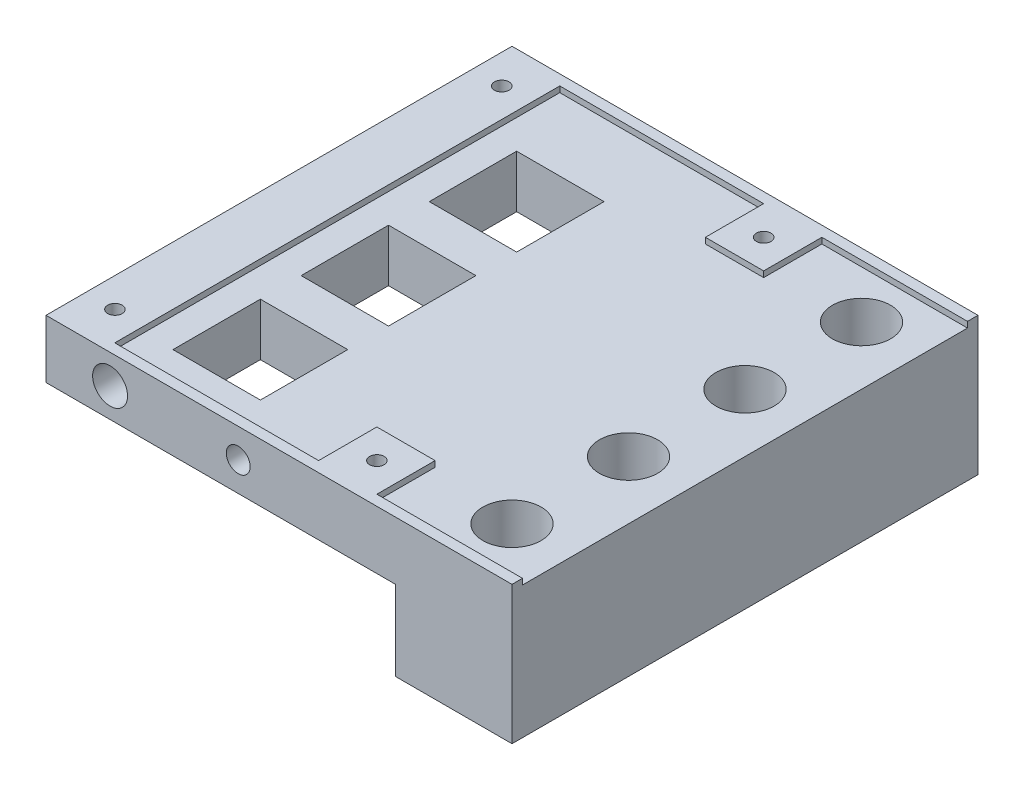
SolidWorks part; units mm, degrees
ref_plane "Front Plane" through (0, 0, 0) normal (0, 0, 1) x (1, 0, 0)
ref_plane "Top Plane" through (0, 0, 0) normal (0, 1, 0) x (1, 0, 0)
ref_plane "Right Plane" through (0, 0, 0) normal (1, 0, 0) x (0, 0, -1)
sketch "Sketch1" plane through (0, 0, 0) normal (0, 1, 0) x (1, 0, 0)
  line L1 (-77.5607, 49.5304) -> (2.4393, 49.5304)
  line L2 (-77.5607, 49.5304) -> (-77.5607, -30.4696)
  line L3 (-77.5607, -30.4696) -> (2.4393, -30.4696)
  line L4 (2.4393, 49.5304) -> (2.4393, -30.4696)
  dimension "D1" = 80
  dimension "D2" = 80
extrude "Boss-Extrude1" add sketch "Sketch1" along normal blind 23.7
sketch "Sketch2" plane through (0, 23.7, 0) normal (0, 1, 0) x (1, 0, 0)
  line L0 (2.4393, -30.4696) -> (2.4393, 49.5304) construction
  line L1 (2.4393, -28.6696) -> (-22.5607, -28.6696)
  line L2 (2.4393, -28.6696) -> (2.4393, 47.7304)
  line L3 (2.4393, 47.7304) -> (-22.5607, 47.7304)
  line L4 (-67.5607, -28.6696) -> (-67.5607, 47.7304)
  line L5 (-77.5607, 49.5304) -> (-77.5607, -30.4696) construction
  line L6 (-77.5607, 9.5304) -> (2.4393, 9.5304) construction
  line L8 (-32.5607, 47.7304) -> (-32.5607, 37.7304)
  line L9 (-32.5607, 37.7304) -> (-22.5607, 37.7304)
  line L10 (-22.5607, 47.7304) -> (-22.5607, 37.7304)
  line L11 (-32.5607, -18.6696) -> (-22.5607, -18.6696)
  line L12 (-22.5607, -28.6696) -> (-22.5607, -18.6696)
  line L14 (-32.5607, -28.6696) -> (-32.5607, -18.6696)
  line L15 (-32.5607, -28.6696) -> (-67.5607, -28.6696)
  line L16 (-32.5607, 47.7304) -> (-67.5607, 47.7304)
  point P6 (-67.5607, 9.5304)
  point P9 (-77.5607, 9.5304)
  dimension "D1" = 76.4
  dimension "D2" = 10
  dimension "D3" = 10
  dimension "D4" = 10
  dimension "D5" = 35
extrude "Cut-Extrude1" cut sketch "Sketch2" against normal blind 1
sketch "Sketch3" plane through (0, 22.7, 0) normal (0, 1, 0) x (1, 0, 0)
  line L0 (-67.5607, 47.7304) -> (-67.5607, -28.6696) construction
  line L1 (-62.5607, -23.6696) -> (-47.5607, -23.6696)
  line L2 (-62.5607, -23.6696) -> (-62.5607, -8.6696)
  line L3 (-62.5607, -8.6696) -> (-47.5607, -8.6696)
  line L4 (-47.5607, -23.6696) -> (-47.5607, -8.6696)
  line L5 (-22.5607, -28.6696) -> (2.4393, -28.6696) construction
  line L6 (-62.5607, -1.6696) -> (-62.5607, 13.3304)
  line L7 (-62.5607, -1.6696) -> (-47.5607, -1.6696)
  line L8 (-47.5607, -1.6696) -> (-47.5607, 13.3304)
  line L9 (-62.5607, 13.3304) -> (-47.5607, 13.3304)
  line L10 (-62.5607, 20.3304) -> (-62.5607, 35.3304)
  line L11 (-62.5607, 20.3304) -> (-47.5607, 20.3304)
  line L12 (-47.5607, 20.3304) -> (-47.5607, 35.3304)
  line L13 (-62.5607, 35.3304) -> (-47.5607, 35.3304)
  dimension "D1" = 15
  dimension "D2" = 15
  dimension "D3" = 5
  dimension "D4" = 5
  dimension "D5" = 3
extrude "Cut-Extrude2" cut sketch "Sketch3" against normal through all
sketch "Sketch4" plane through (0, 0, 30.4696) normal (0, 0, 1) x (1, 0, 0)
  line L0 (-77.5607, 23.7) -> (2.4393, 23.7) construction
  line L1 (-77.5607, 0) -> (-17.5607, 0)
  line L2 (-77.5607, 0) -> (-77.5607, 13.7)
  line L3 (-77.5607, 13.7) -> (-17.5607, 13.7)
  line L4 (-17.5607, 0) -> (-17.5607, 13.7)
  line L5 (2.4393, 23.7) -> (2.4393, 0) construction
  dimension "D1" = 10
  dimension "D2" = 20
extrude "Cut-Extrude3" cut sketch "Sketch4" against normal through all
sketch "Sketch5" plane through (0, 0, 30.4696) normal (0, 0, 1) x (1, 0, 0)
  line L0 (-77.5607, 23.7) -> (-77.5607, 13.7) construction
  line L1 (-62.5607, 13.7) -> (-62.5607, 22.7) construction
  line L2 (-47.5607, 13.7) -> (-47.5607, 22.7) construction
  circle A0 centre (-66.5607, 18.7) radius 3
  circle A1 centre (-44.5607, 18.7) radius 2.05
  point P5 (-77.5607, 18.7)
  dimension "D1" = 6
  dimension "D3" = 4.1
  dimension "D4" = 3
  dimension "D2" = 4
extrude "Cut-Extrude4" cut sketch "Sketch5" against normal through all
sketch "Sketch6" plane through (0, 22.7, 0) normal (0, 1, 0) x (1, 0, 0)
  line L0 (-7.5607, 47.7304) -> (-7.5607, -28.6696) construction
  line L1 (2.4393, 47.7304) -> (-22.5607, 47.7304) construction
  line L2 (-22.5607, -28.6696) -> (2.4393, -28.6696) construction
  line L3 (2.4393, -28.6696) -> (2.4393, 47.7304) construction
  line L4 (-77.5607, -30.4696) -> (2.4393, -30.4696) construction
  point P8 (-7.5607, -20.4696)
  point P9 (-7.5607, -0.4696)
  point P10 (-7.5607, 19.5304)
  point P11 (-7.5607, 39.5304)
  dimension "D1" = 10
  dimension "D2" = 10
  dimension "D3" = 20
  dimension "D4" = 20
  dimension "D5" = 20
hole_wizard "CBORE for M5 Hex Socket Head Cap1" positions "Sketch7" profile "Sketch8" counterbore size "M5" standard "BSI" end condition up to next
sketch "Sketch7" plane through (0, 22.7, 0) normal (0, 1, 0) x (1, 0, 0)
  point P0 (-7.5607, -20.4696)
  point P3 (-7.5607, -0.4696)
  point P6 (-7.5607, 19.5304)
  point P9 (-7.5607, 39.5304)
sketch "Sketch8" plane through (-7.5607, 22.7, 20.4696) normal (1, 0, 0) x (0, 0, 1)
  line L0 (0, 0) -> (0, 22.7)
  line L1 (0, 22.7) -> (2.75, 22.7)
  line L3 (2.75, 22.7) -> (2.75, 15)
  line L4 (2.75, 15) -> (5, 15)
  line L5 (5, 15) -> (5, 0)
  line L7 (5, 0) -> (0, 0)
  line L11 (0, -6.35) -> (0, 107.95) construction
  dimension "Thru Hole Dia." = 5.5
  dimension "Thru Hole Depth" = 22.7
  dimension "C'Bore Dia." = 10
  dimension "C'Bore Depth" = 15
sketch "Sketch9" plane through (0, 23.7, 0) normal (0, 1, 0) x (1, 0, 0)
  line L0 (-32.5607, 37.7304) -> (-32.5607, 47.7304) construction
  line L1 (-22.5607, 37.7304) -> (-32.5607, 37.7304) construction
  line L2 (-77.5607, 9.5304) -> (10.7906, 9.5304) construction
  line L3 (-77.5607, 49.5304) -> (-77.5607, -30.4696) construction
  point P0 (-27.5607, 42.7304)
  point P3 (-32.5607, 42.7304)
  point P4 (-27.5607, -23.6696)
  point P7 (-27.5607, 37.7304)
  point P8 (-72.5233, -23.6696)
  point P14 (-72.5233, 42.7304)
hole_wizard "M3x0.5 Tapped Hole1" positions "Sketch10" profile "Sketch11" tap size "M3x0.5" standard "BSI" end condition up to next
sketch "Sketch10" plane through (0, 23.7, 0) normal (0, 1, 0) x (1, 0, 0)
  point P0 (-27.5607, -23.6696)
  point P3 (-27.5607, 42.7304)
  point P7 (-72.5233, -23.6696)
  point P10 (-72.5233, 42.7304)
sketch "Sketch11" plane through (-27.5607, 23.7, 23.6696) normal (1, 0, 0) x (0, 0, 1)
  line L0 (0, 0) -> (0, 10)
  line L1 (0, 10) -> (1.25, 10)
  line L2 (1.25, 10) -> (1.25, 0)
  line L5 (1.25, 0) -> (0, 0)
  line L11 (0, -6.35) -> (0, 107.95) construction
  dimension "Thru Tap Drill Dia." = 2.5
  dimension "Thru Tap Drill Depth" = 10
cosmetic thread "Hole Thread1" parameters "D2"=3
cosmetic thread "Hole Thread2" parameters "D2"=3
cosmetic thread "Hole Thread3" parameters "D2"=3
cosmetic thread "Hole Thread4" parameters "D2"=3
ref_axis "Axis1" through (-66.5607, 18.7, -49.5304) along (0, 0, 1)
ref_axis "Axis2" through (-44.5607, 18.7, -49.5304) along (0, 0, 1)
sketch "Sketch12" plane through (0, 13.7, 0) normal (0, -1, 0) x (1, 0, 0)
  line L0 (-17.5607, 30.4696) -> (-77.5607, 30.4696) construction
  line L4 (-66.5607, -49.5304) -> (-66.5607, 30.4696) construction
  line L5 (-44.5607, -49.5304) -> (-44.5607, 30.4696) construction
  line L6 (-77.5607, -9.5304) -> (-21.3569, -9.5304) construction
  line L7 (-77.5607, -49.5304) -> (-77.5607, 30.4696) construction
  point P0 (-66.5607, 15.4696)
  point P1 (-44.5607, 15.4696)
  point P5 (-44.5607, -34.5304)
  point P6 (-66.5607, -34.5304)
  dimension "D1" = 15
hole_wizard "M2x0.4 Tapped Hole1" positions "Sketch13" profile "Sketch14" tap size "M2x0.4" standard "BSI" end condition up to next
sketch "Sketch13" plane through (0, 13.7, 0) normal (0, -1, 0) x (-1, 0, 0)
  point P0 (66.5607, -15.4696)
  point P3 (44.5607, -15.4696)
  point P6 (66.5607, 34.5304)
  point P9 (44.5607, 34.5304)
sketch "Sketch14" plane through (-66.5607, 13.7, 15.4696) normal (1, 0, 0) x (0, 0, -1)
  line L0 (0, 0) -> (0, 2)
  line L1 (0, 2) -> (0.8, 2)
  line L2 (0.8, 2) -> (0.8, 0)
  line L5 (0.8, 0) -> (0, 0)
  line L11 (0, -6.35) -> (0, 107.95) construction
  dimension "Thru Tap Drill Dia." = 1.6
  dimension "Thru Tap Drill Depth" = 2
cosmetic thread "Hole Thread5" parameters "D2"=2
cosmetic thread "Hole Thread6" parameters "D2"=2
cosmetic thread "Hole Thread7" parameters "D2"=2
cosmetic thread "Hole Thread8" parameters "D2"=2
